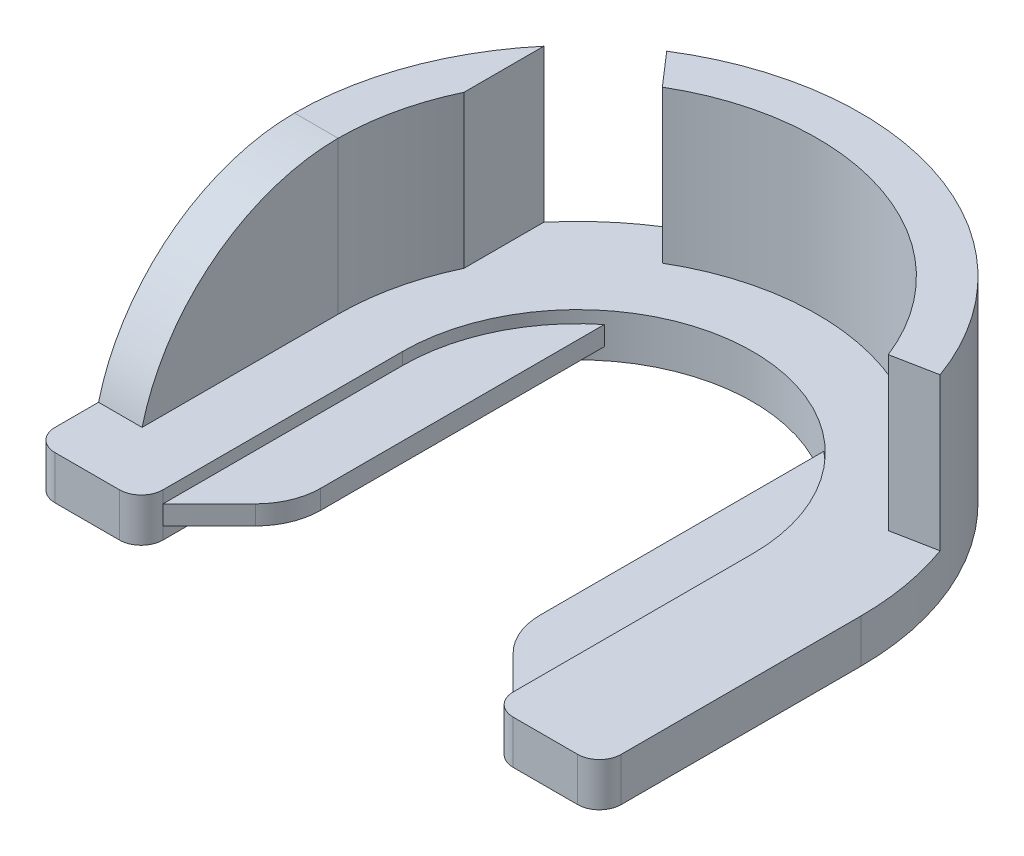
SolidWorks part; units mm, degrees
ref_plane "Front Plane" through (0, 0, 0) normal (0, 0, 1) x (1, 0, 0)
ref_plane "Top Plane" through (0, 0, 0) normal (0, 1, 0) x (1, 0, 0)
ref_plane "Right Plane" through (0, 0, 0) normal (1, 0, 0) x (0, 0, -1)
sketch "Sketch3" plane through (0, 0, 0) normal (0, 1, 0) x (1, 0, 0)
  line L0 (65, 0) -> (65, -55)
  line L1 (-65, 0) -> (65, 0) construction
  line L2 (60, -60) -> (45.2, -60)
  line L3 (40.2, -55) -> (40.2, 0)
  line L4 (25.2, -33.7868) -> (25.2, 31.3209)
  line L5 (29.5934, -44.3934) -> (40.2, -55)
  line L6 (54.9988, 0) -> (54.9988, -60)
  line L7 (0, -81.5957) -> (0, 81.5957) construction
  line L8 (-54.9988, 0) -> (-54.9988, -60)
  line L9 (-29.5934, -44.3934) -> (-40.2, -55)
  line L10 (-25.2, -33.7868) -> (-25.2, 31.3209)
  line L11 (-40.2, -55) -> (-40.2, 0)
  line L12 (-60, -60) -> (-45.2, -60)
  line L13 (-65, 0) -> (-65, -55)
  arc A0 (65, 0) -> (-65, 0) centre (0, 0) ccw
  arc A1 (40.2, 0) -> (-40.2, 0) centre (0, 0) ccw
  arc A2 (60, -60) -> (65, -55) centre (60, -55) ccw
  arc A3 (45.2, -60) -> (40.2, -55) centre (45.2, -55) cw
  arc A4 (25.2, -33.7868) -> (29.5934, -44.3934) centre (40.2, -33.7868) ccw
  arc A5 (-54.9988, 0) -> (54.9988, 0) centre (0, 0) cw
  arc A6 (-25.2, -33.7868) -> (-29.5934, -44.3934) centre (-40.2, -33.7868) cw
  arc A7 (-45.2, -60) -> (-40.2, -55) centre (-45.2, -55) ccw
  arc A8 (-60, -60) -> (-65, -55) centre (-60, -55) cw
  point P12 (65, -60)
  point P16 (40.2, -60)
  point P19 (25.2, -40)
  point P22 (54.9988, -31.6493)
  point P37 (-25.2, -40)
  point P38 (-40.2, -60)
  point P39 (-65, -60)
  dimension "D1" = 130
  dimension "D4" = 80.4
  dimension "D8" = 5
  dimension "D9" = 15
  dimension "D10" = 54.9988
  dimension "D2" = 60
  dimension "D3" = 24.8
  dimension "D5" = 15
  dimension "D6" = 5
  dimension "D7" = 15
extrude "Boss-Extrude1" add sketch "Sketch3" along normal mid plane 4.4 contours A1 L1 L10 | L1 L11 L9 A6 L10 | L4 L1 A1 | L1 L4 A4 L5 L3 region at (33.1426, 0, 23.8401) region at (31.3077, 0, -12.105) region at (-31.3077, 0, -12.105) region at (-33.1426, 0, 23.8401)
extrude "Boss-Extrude2" add sketch "Sketch3<3>" along normal mid plane 10 contours A5 L1 A1 | L1 L3 A3 L2 L6 | L1 L8 L12 A7 L11 region at (47.6376, 0, 29.8244) region at (47.5994, 0, -1.2298) region at (-47.6376, 0, 29.8244)
sketch "Sketch3<3>" plane through (0, 0, 0) normal (0, 1, 0) x (1, 0, 0) same geometry as "Sketch3"
extrude "Boss-Extrude3" add sketch "Sketch3<4>" against normal blind 5 and the other way blind 40 contours A0 L1 A5 | L1 L13 A8 L12 L8 | L1 L6 L2 A2 L0 region at (59.9643, 0, 29.7394) region at (59.9994, 0, -1.4534) region at (-59.9643, 0, 29.7394)
sketch "Sketch3<4>" plane through (0, 0, 0) normal (0, 1, 0) x (1, 0, 0) same geometry as "Sketch3"
sketch "Sketch4" plane through (0, 0, 0) normal (1, 0, 0) x (0, 0, -1)
  line L0 (-45, 5) -> (-60, 5)
  line L1 (-60, 5) -> (-60, 40)
  line L2 (-60, 40) -> (0, 40)
  line L3 (0, -5) -> (-55, -5) construction
  line L4 (0, 40) -> (-55, 40) construction
  line L5 (-60, 40) -> (-60, -5) construction
  arc A0 (-45, 5) -> (0, 40) centre (0, -6.4286) cw
  point P11 (0, 40)
  point P12 (-8.7505, 40)
  dimension "D2" = 15
  dimension "D1" = 10
extrude "Cut-Extrude1" cut sketch "Sketch4" against normal through all both and the other way through all
sketch "Sketch5" plane through (0, 40, 0) normal (0, 1, 0) x (1, 0, 0)
  line L0 (0, 0) -> (-42.6438, 49.0561) construction
  line L2 (-49.6832, 41.9115) -> (-43.0281, 34.2556) construction
  line L4 (-34.5891, 55.0327) -> (-27.9339, 47.3768)
  line L5 (0, 0) -> (0, 65) construction
  line L6 (-49.6832, 41.9115) -> (-49.6832, 23.5889)
  line L7 (0, 0) -> (63.8058, 12.4026) construction
  line L8 (51.1803, 20.1356) -> (61.1381, 22.0712)
  line L9 (54.9988, 0) -> (54.9988, -45)
  line L10 (54.9988, -45) -> (65, -45)
  line L11 (65, -45) -> (65, 0)
  line L12 (65, -45) -> (65, 0) construction
  line L13 (54.9988, 0) -> (54.9988, -45) construction
  line L14 (54.9988, -45) -> (65, -45) construction
  arc A0 (65, 0) -> (-65, 0) centre (0, 0) ccw construction
  arc A1 (-49.6832, 41.9115) -> (-34.5891, 55.0327) centre (0, 0) cw
  arc A2 (-43.0281, 34.2556) -> (-27.9339, 47.3768) centre (0, 0) cw
  arc A3 (54.9988, 0) -> (-54.9988, 0) centre (0, 0) ccw construction
  arc A4 (-49.6832, 23.5889) -> (-43.0281, 34.2556) centre (0, 0) cw
  arc A5 (54.9988, 0) -> (-54.9988, 0) centre (0, 0) ccw construction
  arc A6 (61.1381, 22.0712) -> (65, 0) centre (0, 0) cw
  arc A7 (51.1803, 20.1356) -> (54.9988, 0) centre (0, 0) cw
  dimension "D2" = 20
  dimension "D3" = 10
  dimension "D4" = 120
  dimension "D1" = 41
  dimension "D6" = 10
extrude "Cut-Extrude2" cut sketch "Sketch5" against normal blind 35
